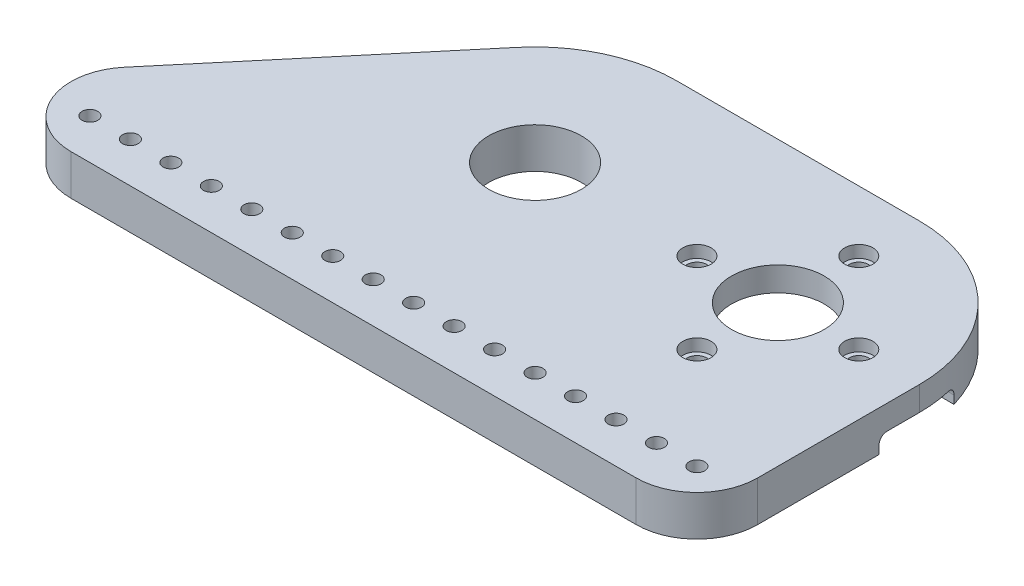
SolidWorks part; units mm, degrees
ref_plane "Front Plane" through (0, 0, 0) normal (0, 0, 1) x (1, 0, 0)
ref_plane "Top Plane" through (0, 0, 0) normal (0, 1, 0) x (1, 0, 0)
ref_plane "Right Plane" through (0, 0, 0) normal (1, 0, 0) x (0, 0, -1)
sketch "Sketch1" plane through (0, 0, 0) normal (0, 1, 0) x (1, 0, 0)
  line L0 (0, 0) -> (76.2, 0) construction
  line L1 (0, 0) -> (76.2, 0) construction
  line L2 (0, 44.45) -> (76.2, 44.45)
  line L3 (0, -44.45) -> (76.2, -44.45)
  line L4 (0, 0) -> (0, -69.85) construction
  line L6 (-116.6365, -69.85) -> (-20.7274, 44.45)
  line L7 (120.65, -69.85) -> (120.65, 44.45)
  line L8 (120.65, 44.45) -> (-20.7274, 44.45)
  line L9 (0, -69.85) -> (-116.6365, -69.85)
  line L10 (0, -69.85) -> (120.65, -69.85)
  line L11 (107.95, -69.85) -> (107.95, -44.45) construction
  line L12 (107.95, -44.45) -> (120.65, -44.45) construction
  circle A0 centre (0, 0) radius 14.551
  arc A1 (0, 44.45) -> (0, -44.45) centre (0, 0) ccw
  arc A2 (76.2, -44.45) -> (76.2, 44.45) centre (76.2, 0) ccw
  circle A3 centre (76.2, 0) radius 14.551
  circle A5 centre (107.95, -57.15) radius 1.27
  point P3 (38.1, 0)
  point P14 (0, -69.85)
  point P20 (107.95, -57.15)
  dimension "D1" = 29.102
  dimension "D6" = 12.7
  dimension "D8" = 2.54
  dimension "D2" = 88.9
  dimension "D3" = 76.2
  dimension "D4" = 90
  dimension "D5" = 50
  dimension "D7" = 25.4
extrude "Initial Plate" add sketch "Sketch1" along normal blind 12.7 contours A2 L3 A1 L6 L9 L10 L7 | A2 L2 A1 L3 A3 A0 region at (38.1, 0, 0) region at (-2.7467, 0, 48.4689)
fillet "Plate Fillet" radius 19.05 2 edges at (120.65, 6.35, 69.85) (-116.6365, 6.35, 69.85)
hole_wizard "#10 (0.1935) Initial Mounting Hole" positions "Sketch3" profile "Sketch4" hole size "#10" standard "ANSI Inch" end condition through all
sketch "Sketch3" plane through (0, 12.7, 0) normal (0, 1, 0) x (1, 0, 0)
  point P0 (107.95, -57.15)
sketch "Sketch4" plane through (107.95, 12.7, 57.15) normal (1, 0, 0) x (0, 0, 1)
  line L0 (0, 0) -> (0, 12.7)
  line L1 (0, 12.7) -> (2.4574, 12.7)
  line L2 (2.4574, 12.7) -> (2.4574, 0)
  line L5 (2.4574, 0) -> (0, 0)
  line L11 (0, -6.35) -> (0, 107.95) construction
  dimension "Thru Hole Dia." = 4.9149
  dimension "Thru Hole Depth" = 12.7
pattern_linear "Mounting Pattern" count 16 spacing 12.7 along (-1, 0, 0) of "#10 (0.1935) Initial Mounting Hole"
sketch "Sketch5" plane through (0, 12.7, 0) normal (0, 1, 0) x (1, 0, 0)
  line L0 (76.2, 25.4) -> (76.2, -25.4) construction
  line L1 (76.2, 0) -> (0, 0) construction
  circle A0 centre (76.2, 0) radius 25.4 construction
  circle A6 centre (76.2, 25.4) radius 3.048
  circle A7 centre (76.2, 25.4) radius 4.445
  dimension "D1" = 50.8
  dimension "D2" = 6.096
  dimension "D3" = 8.89
extrude "Initial NEO ThroughHole" cut sketch "Sketch5" against normal through all contours A6 region at (76.2, 12.7, -25.4)
extrude "Initial NEO Bolt Head Hole" cut sketch "Sketch5<4>" against normal blind 3.81
sketch "Sketch5<4>" plane through (0, 12.7, 0) normal (0, 1, 0) x (1, 0, 0) same geometry as "Sketch5"
pattern_circular "NEO Hole Pattern" count 4 over 360 about axis through (76.2, 12.7, 0) along (0, 1, 0) of "Initial NEO Bolt Head Hole", "Initial NEO ThroughHole"
sketch "Sketch6" plane through (0, 0, 0) normal (0, -1, 0) x (1, 0, 0)
  line L0 (120.65, 50.8) -> (120.65, 0) construction
  line L1 (103.9081, 12.7) -> (120.65, 12.7)
  line L3 (103.9081, -12.7) -> (120.65, -12.7)
  line L4 (120.65, 12.7) -> (120.65, -12.7)
  arc A0 (103.9081, 12.7) -> (103.9081, -12.7) centre (76.2, 0) ccw
  point P3 (106.68, 0)
  dimension "D1" = 60.96
  dimension "D2" = 25.4
extrude "NEO Cutout" cut sketch "Sketch6" against normal blind 5.08
fillet "Fillet1" radius 2.54 2 edges at (111.3526, 5.08, -12.7) (112.2791, 5.08, 12.7)
